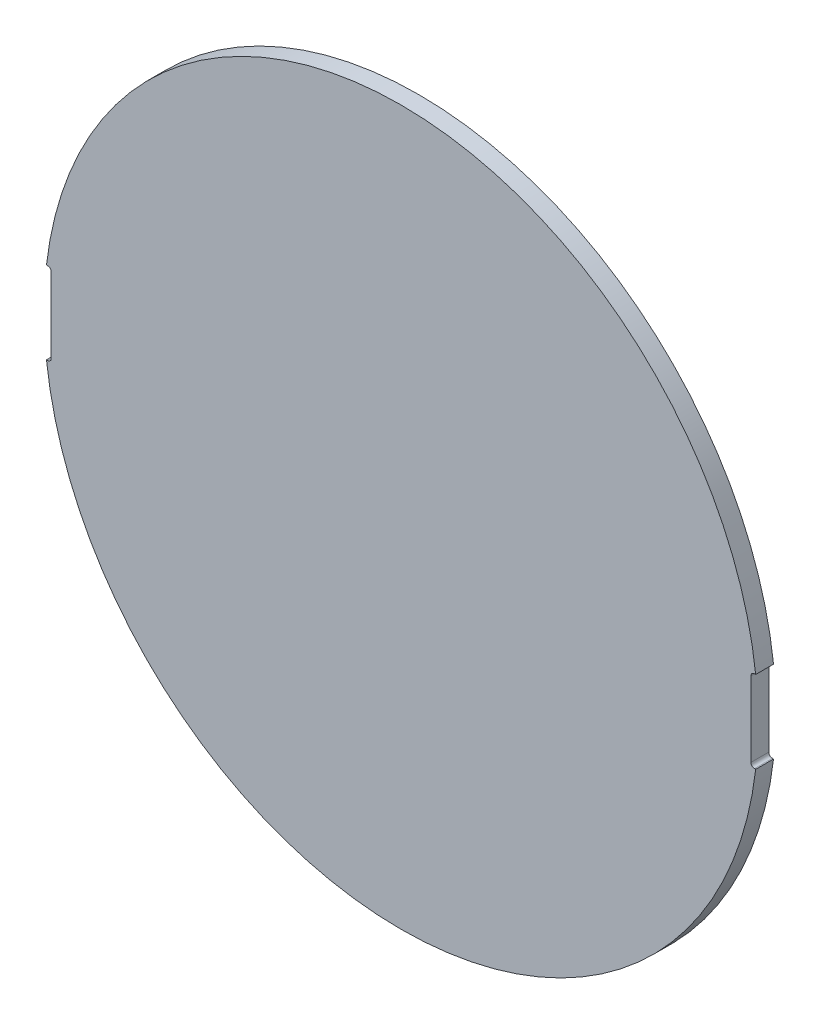
SolidWorks part; units mm, degrees
ref_plane "Front Plane" through (0, 0, 0) normal (0, 0, 1) x (1, 0, 0)
ref_plane "Top Plane" through (0, 0, 0) normal (0, 1, 0) x (1, 0, 0)
ref_plane "Right Plane" through (0, 0, 0) normal (1, 0, 0) x (0, 0, -1)
sketch "Sketch1" plane through (0, 0, 0) normal (0, 0, 1) x (1, 0, 0)
  circle A0 centre (0, 0) radius 20
  dimension "D1" = 40
extrude "Boss-Extrude1" add sketch "Sketch1" along normal blind 1
sketch "Sketch2" plane through (0, 0, 1) normal (0, 0, 1) x (1, 0, 0)
  line L0 (-19.8673, 2.3) -> (-19.8, 2.3)
  line L1 (-19.6, 2.1) -> (-19.6, -2.1)
  line L2 (-19.8, -2.3) -> (-19.8673, -2.3)
  line L3 (-19.8673, 2.3) -> (-20, 2.3) construction
  line L4 (-20, 2.3) -> (-20, -2.3) construction
  line L5 (-20, -2.3) -> (-19.8673, -2.3) construction
  circle A0 centre (0, 0) radius 20 construction
  arc A1 (-19.8673, 2.3) -> (-19.8673, -2.3) centre (0, 0) ccw
  arc A2 (-19.6, -2.1) -> (-19.8, -2.3) centre (-19.8, -2.1) cw
  arc A3 (-19.6, 2.1) -> (-19.8, 2.3) centre (-19.8, 2.1) ccw
  point P4 (-19.6, 0)
  point P13 (-19.6, -2.3)
  point P16 (-19.6, 2.3)
  dimension "D3" = 0.2
  dimension "D1" = 0.4
  dimension "D2" = 4.6
extrude "Cut-Extrude1" cut sketch "Sketch2" against normal up to next
pattern_circular "CirPattern1" count 2 every 180 about axis through (0, 0, 1) along (0, 0, 1) of "Cut-Extrude1"
ref_axis "Axis1" through (0, 0, -0.05) along (0, 0, 1)
